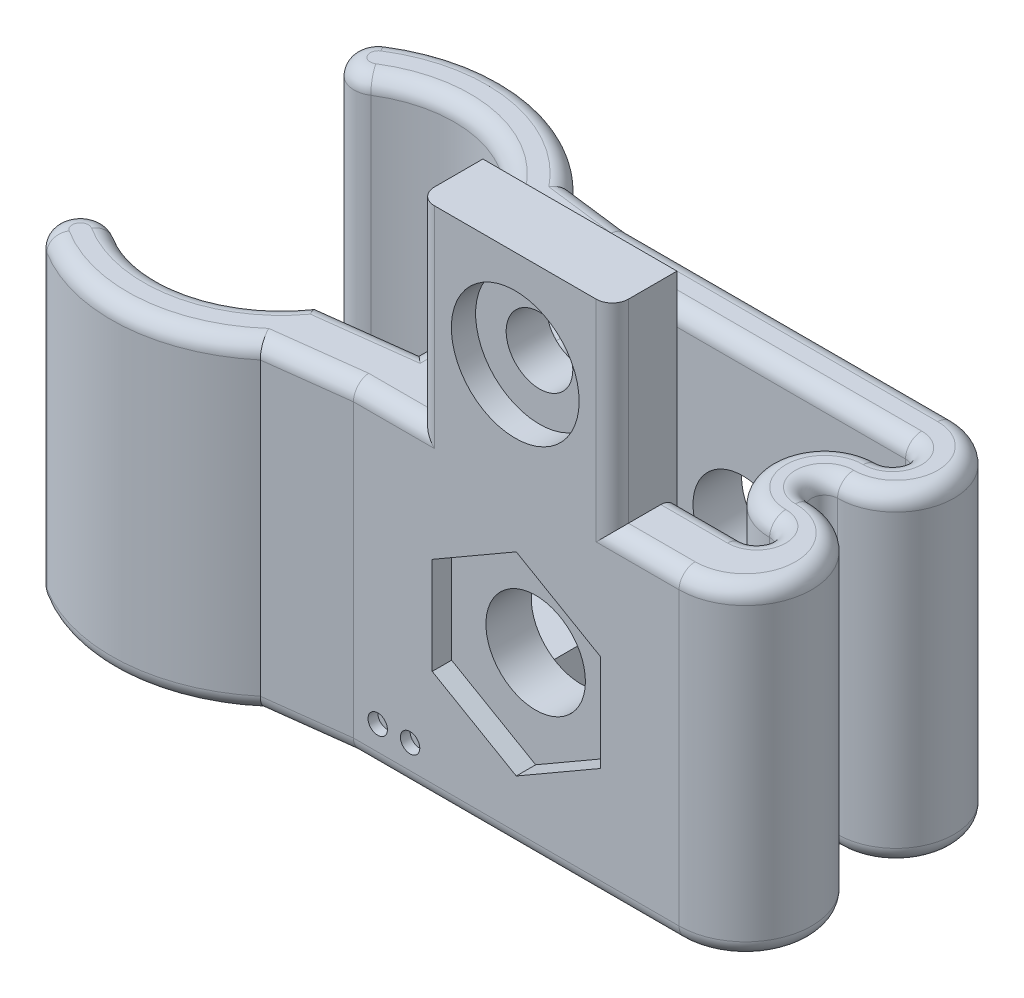
SolidWorks part; units mm, degrees
ref_plane "Front Plane" through (0, 0, 0) normal (0, 0, 1) x (1, 0, 0)
ref_plane "Top Plane" through (0, 0, 0) normal (0, 1, 0) x (1, 0, 0)
ref_plane "Right Plane" through (0, 0, 0) normal (1, 0, 0) x (0, 0, -1)
sketch "Sketch2" plane through (0, 0, 0) normal (0, 1, 0) x (1, 0, 0)
  line L0 (0, 0) -> (32, 0) construction
  line L1 (0, 0) -> (0, 1.6) construction
  line L2 (0, 0) -> (0, -1.6) construction
  line L3 (32, 0) -> (32, 5) construction
  line L4 (32, 0) -> (32, -5) construction
  line L5 (32, 5) -> (6, 5) construction
  line L6 (32, -5) -> (6, -5) construction
  line L7 (11.8739, 5) -> (32, 5)
  line L8 (11.8739, -5) -> (32, -5)
  line L9 (32, 8) -> (11.8739, 8)
  line L10 (32, -9) -> (11.8739, -9)
  line L11 (11.8739, 5) -> (6.2801, 5.7)
  line L12 (11.8739, 8) -> (7.919, 8.4949)
  line L13 (11.8739, -5) -> (6.2801, -5.7)
  line L14 (11.8739, -9) -> (6.7523, -9.6409)
  arc A0 (6.2801, 5.7) -> (-4, 7.9443) centre (0, 1.6) ccw
  arc A1 (6.2801, -5.7) -> (-4, -7.9443) centre (0, -1.6) cw
  arc A2 (32, 5) -> (32, 3.4) centre (32, 4.2) cw
  arc A3 (32, 3.4) -> (32, -3.4) centre (32, 0) ccw
  arc A4 (32, -3.4) -> (32, -5) centre (32, -4.2) cw
  arc A5 (-4, 7.9443) -> (-5.6, 10.482) centre (-4.8, 9.2131) cw
  arc A6 (-4, -7.9443) -> (-5.6, -10.482) centre (-4.8, -9.2131) ccw
  arc A7 (-5.6, 10.482) -> (7.919, 8.4949) centre (0, 1.6) cw
  arc A8 (-5.6, -10.482) -> (6.7523, -9.6409) centre (0, -1.6) ccw
  arc A9 (32, -9) -> (32, -0.8) centre (32, -4.9) ccw
  arc A10 (32, -0.8) -> (32, 0.8) centre (32, 0) cw
  arc A11 (32, 0.8) -> (32, 8) centre (32, 4.4) ccw
  dimension "D6" = 7.5
  dimension "D7" = 7.5
  dimension "D8" = 0.8
  dimension "D9" = 0.8
  dimension "D11" = 1.5
  dimension "D12" = 1.5
  dimension "D14" = 10.5
  dimension "D16" = 10.5
  dimension "D17" = 0.8
  dimension "D18" = 11.8739
  dimension "D1" = 1.6
  dimension "D2" = 1.6
  dimension "D3" = 32
  dimension "D4" = 5
  dimension "D5" = 5
  dimension "D10" = 4
  dimension "D13" = 3
  dimension "D15" = 4
  dimension "D19" = 0.7
extrude "Boss-Extrude1" add sketch "Sketch2" along normal blind 20
sketch "Sketch3" plane through (0, 0, -8) normal (0, 0, -1) x (-1, 0, 0)
  line L0 (-21.9369, 20) -> (-21.9369, 0) construction
  line L1 (-32, 20) -> (-11.8739, 20) construction
  line L2 (-32, 0) -> (-11.8739, 0) construction
  circle A0 centre (-21.9369, 10) radius 3.075
  dimension "D1" = 6.15
extrude "Cut-Extrude1" cut sketch "Sketch3" against normal through all
sketch "Sketch4" plane through (0, 0, 9) normal (0, 0, 1) x (1, 0, 0)
  line L0 (21.9369, 6.925) -> (21.9369, 13.075) construction
  line L2 (21.9369, 4) -> (27.1331, 7)
  line L3 (27.1331, 7) -> (27.1331, 13)
  line L4 (27.1331, 13) -> (21.9369, 16)
  line L5 (21.9369, 16) -> (16.7408, 13)
  line L6 (16.7408, 13) -> (16.7408, 7)
  line L7 (16.7408, 7) -> (21.9369, 4)
  circle A0 centre (21.9369, 10) radius 3.075 construction
  circle A1 centre (21.9369, 10) radius 6 construction
  dimension "D1" = 12
extrude "Cut-Extrude2" cut sketch "Sketch4" against normal blind 1.2
sketch "Sketch5" plane through (0, 20, 0) normal (0, 1, 0) x (1, 0, 0)
  line L0 (32, -5) -> (11.8739, -5) construction
  line L1 (27.8739, -9) -> (15.8739, -9)
  line L2 (27.8739, -9) -> (27.8739, -5)
  line L3 (27.8739, -5) -> (15.8739, -5)
  line L4 (15.8739, -9) -> (15.8739, -5)
  dimension "D1" = 12
  dimension "D2" = 4
extrude "Boss-Extrude2" add sketch "Sketch5" along normal blind 12
sketch "Sketch6" plane through (0, 0, 9) normal (0, 0, 1) x (1, 0, 0)
  line L0 (15.8739, 26) -> (27.8739, 26) construction
  line L1 (15.8739, 32) -> (15.8739, 20) construction
  line L2 (27.8739, 32) -> (27.8739, 20) construction
  circle A0 centre (21.8739, 26) radius 2.06
  dimension "D1" = 4.12
extrude "Cut-Extrude3" cut sketch "Sketch6" against normal through all
sketch "Sketch7" plane through (0, 0, 0) normal (0, -1, 0) x (1, 0, 0)
  line L0 (11.8739, 5) -> (11.8739, -1.8)
  line L1 (32, 5) -> (11.8739, 5) construction
  line L2 (16.8739, 5) -> (16.8739, -2.3)
  line L3 (11.8739, 5) -> (16.8739, 5)
  line L4 (11.8739, -1.8) -> (16.8739, -2.3)
  dimension "D1" = 11.8739
  dimension "D2" = 6.8
  dimension "D3" = 7.3
  dimension "D4" = 5
extrude "Boss-Extrude3" add sketch "Sketch7" against normal blind 4
extrude "Boss-Extrude4" add sketch "Sketch7<2>" against normal blind 4 from offset 16 offset against normal yes
sketch "Sketch7<2>" plane through (0, 0, 0) normal (0, -1, 0) x (1, 0, 0) same geometry as "Sketch7"
sketch "Sketch8" plane through (0, 0, 9) normal (0, 0, 1) x (1, 0, 0)
  circle A0 centre (21.8739, 26) radius 3.95
  dimension "D1" = 7.9
extrude "Cut-Extrude4" cut sketch "Sketch8" against normal blind 1.5
fillet "Fillet1" radius 1 23 edges at (28.6, 0, 0) (32.8, 0, 4.2) (24.4369, 0, 5) (16.8739, 0, 1.35) (14.3739, 0, -2.05) (11.8739, 0, 1.6) (1.5997, 0, 8.9274) (-6.0689, 0, 8.4131) (0.7133, 0, 12.0757) (21.9369, 0, 9) (36.1, 0, 4.9) (31.2, 0, 0) (35.6, 0, -4.4) (21.9369, 0, -8) (1.5269, 0, -11.9884) (-6.0689, 0, -8.4131) (1.5997, 0, -8.9274) (21.9369, 0, -5) (32.8, 0, -4.2) (9.8964, 0, -8.2475) (9.077, 0, -5.35) (9.077, 0, 5.35) (9.3131, 0, 9.3205)
fillet "Fillet7" radius 1 2 edges
fillet "Fillet10" radius 1 15 edges at (21.9369, 20, -8) (35.6, 20, -4.4) (31.2, 20, 0) (36.1, 20, 4.9) (32.8, 20, 4.2) (28.6, 20, 0) (32.8, 20, -4.2) (21.9369, 20, -5) (9.077, 20, -5.35) (1.5997, 20, -8.9274) (-6.0689, 20, -8.4131) (1.5269, 20, -11.9884) (9.8964, 20, -8.2475)
fillet "Fillet11" radius 1 9 edges at (9.3131, 20, 9.3205) (0.7133, 20, 12.0757) (-6.0689, 20, 8.4131) (1.5997, 20, 8.9274) (9.077, 20, 5.35) (16.8739, 20, 1.35) (14.3739, 20, -2.05) (11.8739, 20, 1.6)
sketch "Sketch9" plane through (0, 0, 9) normal (0, 0, 1) x (1, 0, 0)
  line L0 (11.8739, 1) -> (32, 1) construction
  line L1 (11.8739, 19) -> (11.8739, 1) construction
  circle A0 centre (13.3739, 2.5) radius 0.6
  circle A1 centre (15.3739, 2.5) radius 0.6
  dimension "D1" = 1.2
  dimension "D4" = 1.2
  dimension "D2" = 1.5
  dimension "D3" = 1.5
  dimension "D5" = 2
extrude "Cut-Extrude5" cut sketch "Sketch9" against normal blind 0.6
